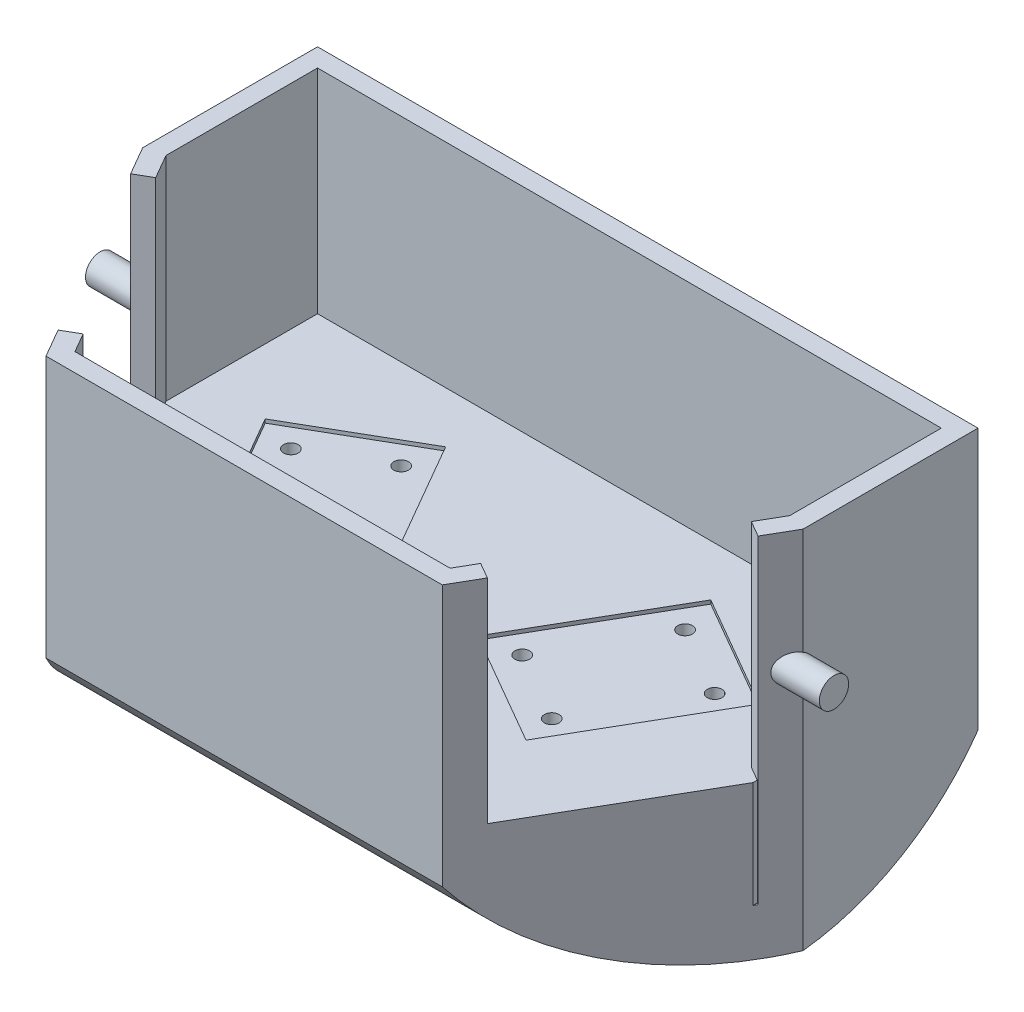
SolidWorks part; units mm, degrees
ref_plane "Front Plane" through (0, 0, 0) normal (0, 0, 1) x (1, 0, 0)
ref_plane "Top Plane" through (0, 0, 0) normal (0, 1, 0) x (1, 0, 0)
ref_plane "Right Plane" through (0, 0, 0) normal (1, 0, 0) x (0, 0, -1)
sketch "Sketch2" plane through (0, 0, 0) normal (0, 1, 0) x (1, 0, 0)
  line L0 (-54, -55) -> (-90, 7.3538)
  line L1 (-90, -55) -> (90, -55)
  line L2 (-90, -55) -> (-90, 55)
  line L3 (-90, 55) -> (90, 55)
  line L4 (90, -55) -> (90, 55)
  line L5 (-90, -55) -> (90, 55) construction
  line L6 (-90, 55) -> (90, -55) construction
  line L7 (0, -55) -> (0, 55) construction
  line L8 (54, -55) -> (90, 7.3538)
  point P0 (0, 0)
  dimension "D1" = 110
  dimension "D2" = 180
  dimension "D3" = 72
  dimension "D4" = 30
extrude "Boss-Extrude1" add sketch "Sketch2" along normal blind 50 and the other way blind 50 contours L1 L8 L4 L3 L2 L0 region at (0, 0, -4.375)
sketch "Sketch13" plane through (-90, 0, 0) normal (-1, 0, 0) x (0, 0, 1)
  line L0 (55, -50) -> (55, 50) construction
  line L1 (-55, -50) -> (55, -50)
  line L2 (-55, -50) -> (-55, -21.2688)
  line L3 (-55, -21.2688) -> (55, -21.2688)
  line L4 (55, -50) -> (55, -21.2688)
  line L5 (-55, -21.2688) -> (-55, -50)
  line L6 (-55, -50) -> (55, -50)
  line L7 (55, -50) -> (55, -21.2688)
  arc A1 (-55, -21.2688) -> (55, -21.2688) centre (0, 17.2426) ccw
  point P8 (0, -49.9)
  line M1 (-7.3538, -50) -> (-7.3538, 50)
  line M3 (-55, 50) -> (-55, -50)
  line M4 (-55, -50) -> (-7.3538, -50)
  dimension "D1" = 67.1426
  dimension "D2" = 0.1
extrude "Cut-Extrude9" cut sketch "Sketch13" against normal up to next contours A1 M3 M4 M1 | A1 L1 L4 M1 region at (-90, -41.8172, -41.8726) region at (-90, -41.8753, 41.57)
shell "Shell1" thickness 5 removed face at (0, 50, -2.4513)
sketch "Sketch5" plane through (-64.3157, 0, 37.1327) normal (-0.866, 0, 0.5) x (0.5, 0, 0.866)
  line L0 (20.6314, 50) -> (-51.3686, 50) construction
  line L1 (-42.3686, 50) -> (11.6314, 50)
  line L2 (-42.3686, 50) -> (-42.3686, -37)
  line L3 (-42.3686, -37) -> (11.6314, -37)
  line L4 (11.6314, 50) -> (11.6314, -37)
  line L6 (20.6314, -21.2688) -> (20.6314, 50) construction
  dimension "D1" = 87
  dimension "D2" = 54
  dimension "D3" = 9
extrude "Cut-Extrude2" cut sketch "Sketch5" against normal blind 5
mirror "Mirror1" about plane through (0, 0, 0) normal (1, 0, 0) of "Cut-Extrude2"
sketch "Sketch16" plane through (-85, 0, 0) normal (1, 0, 0) x (0, 0, -1)
  line L0 (-55, -8) -> (55, -8)
  line L1 (-55, -21.2688) -> (-55, 50) construction
  line L2 (55, -21.2688) -> (55, 50) construction
  line L3 (-55, -8) -> (-55, -21.2688)
  line L4 (55, -8) -> (55, -21.2688)
  line L5 (7.3538, 50) -> (55, 50) construction
  arc A0 (-55, -21.2688) -> (55, -21.2688) centre (0, 17.2426) ccw
  dimension "D1" = 58
extrude "Boss-Extrude4" add sketch "Sketch16" along normal up to surface (170 mm away) up to face at (85, 7.9737, -29.9666)
sketch "Sketch6" plane through (0, -8, 0) normal (0, 1, 0) x (1, 0, 0)
  line L0 (-36.1276, 36.0441) -> (-12.8776, -4.2261)
  line L1 (-36.1276, 36.0441) -> (-67.3045, 18.0441)
  line L2 (-12.8776, -4.2261) -> (-44.0545, -22.2261)
  line L3 (-67.3045, 18.0441) -> (-44.0545, -22.2261)
  line L6 (-51.1132, -50) -> (-54.1699, -44.7058) construction
  line L13 (-38.6898, 26.4819) -> (-22.4398, -1.6639)
  line L14 (-22.4398, -1.6639) -> (-41.4923, -12.6639)
  line L15 (-57.7423, 15.4819) -> (-41.4923, -12.6639)
  line L16 (-38.6898, 26.4819) -> (-57.7423, 15.4819)
  line L17 (0, -73.8569) -> (0, 73.8569) construction
  line L18 (12.8776, -4.2261) -> (44.0545, -22.2261)
  line L19 (67.3045, 18.0441) -> (44.0545, -22.2261)
  line L20 (36.1276, 36.0441) -> (67.3045, 18.0441)
  line L21 (36.1276, 36.0441) -> (12.8776, -4.2261)
  circle A8 centre (-57.7423, 15.4819) radius 2
  circle A9 centre (-38.6898, 26.4819) radius 2
  circle A10 centre (-41.4923, -12.6639) radius 2
  circle A11 centre (-22.4398, -1.6639) radius 2
  circle A12 centre (22.4398, -1.6639) radius 2
  circle A13 centre (41.4923, -12.6639) radius 2
  circle A14 centre (38.6898, 26.4819) radius 2
  circle A15 centre (57.7423, 15.4819) radius 2
  dimension "D4" = 7
  dimension "D5" = 4
  dimension "D6" = 4
  dimension "D7" = 4
  dimension "D9" = 4
  dimension "D1" = 20
  dimension "D2" = 46.5
  dimension "D3" = 36
  dimension "D8" = 0.75
extrude "Cut-Extrude4" cut sketch "Sketch6" against normal through all contours A8 | A9 | A10 | A11 | A12 | A14 | A15 | A13
extrude "Cut-Extrude5" cut sketch "Sketch6<4>" against normal blind 1 contours L20 L21 L18 L19 A14 A12 A13 A15 | L0 L1 L3 L2 region at (40.091, -8, -6.909)
sketch "Sketch6<4>" plane through (0, -8, 0) normal (0, 1, 0) x (1, 0, 0) same geometry as "Sketch6"
sketch "Sketch17" plane through (0, -8, 0) normal (0, 1, 0) x (1, 0, 0)
  line L0 (-54, -55) -> (-85, -55)
  line L1 (-54, -55) -> (-85, -55) construction
  line L2 (-85, -55) -> (-85, -1.3064)
  line L3 (-85, -1.3064) -> (-54, -55)
  line L4 (85, -55) -> (54, -55)
  line L5 (54, -55) -> (85, -1.3064)
  line L6 (85, -1.3064) -> (85, -55)
extrude "Cut-Extrude10" cut sketch "Sketch17" against normal up to next
sketch "Sketch18" plane through (-90, 0, 0) normal (-1, 0, 0) x (0, 0, 1)
  line L0 (55, -21.2688) -> (55, 50) construction
  arc A0 (-55, -21.2688) -> (55, -21.2688) centre (0, 17.2426) ccw
  circle A1 centre (-5.7558, 17.2426) radius 4
  dimension "D1" = 8
extrude "Boss-Extrude5" add sketch "Sketch18" along normal blind 10 and the other way up to body separate body contours A1
mirror "Mirror2" about plane through (0, 0, 0) normal (1, 0, 0) of "Boss-Extrude5"
